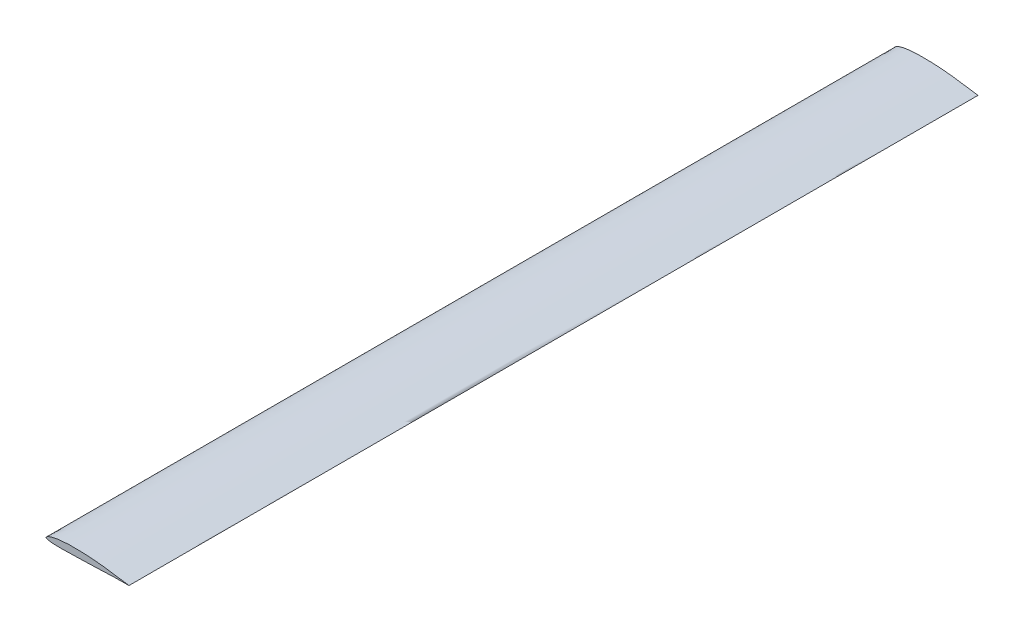
SolidWorks part; units mm, degrees
material "EPP"
ref_plane "Front Plane" through (0, 0, 0) normal (0, 0, 1) x (1, 0, 0)
ref_plane "Top Plane" through (0, 0, 0) normal (0, 1, 0) x (1, 0, 0)
ref_plane "Right Plane" through (0, 0, 0) normal (1, 0, 0) x (0, 0, -1)
curve "Curve1"
  spline degree 3 poles (174.7733, 0.0316, 0) (176.3111, -0.0187, 0) (174.7757, 0.116, 0) (173.5399, 0.2928, 0) (170.5766, 0.6845, 0) (166.994, 1.2316, 0) (162.3909, 1.9531, 0) (157.0465, 2.8136, 0) (150.9809, 3.7843, 0) (144.3051, 4.8259, 0) (137.096, 5.8948, 0) (129.4315, 6.9383, 0) (121.3831, 7.9192, 0) (113.0236, 8.817, 0) (104.4335, 9.6175, 0) (95.705, 10.3199, 0) (86.9339, 10.9107, 0) (78.2102, 11.3525, 0) (69.6201, 11.6329, 0) (61.2465, 11.7525, 0) (53.1672, 11.6898, 0) (45.4565, 11.4373, 0) (38.1834, 11.0163, 0) (31.4143, 10.4177, 0) (25.2077, 9.6463, 0) (19.6117, 8.718, 0) (14.6681, 7.6521, 0) (10.4108, 6.4684, 0) (6.8656, 5.2, 0) (4.0438, 3.8827, 0) (1.9667, 2.5734, 0) (0.8028, 1.5368, 0) (0.3168, 0.8428, 0) (0.1437, 0.5358, 0) (0.0368, 0.2599, 0) (-0.0054, 0.0423, 0) (0.0031, -0.1291, 0) (0.087, -0.2829, 0) (0.2444, -0.4592, 0) (0.4965, -0.6637, 0) (1.1068, -1.0427, 0) (2.4658, -1.5967, 0) (4.8509, -2.2112, 0) (8.2278, -2.7728, 0) (12.4572, -3.2321, 0) (17.5091, -3.5742, 0) (23.3419, -3.7993, 0) (29.9045, -3.9095, 0) (37.1348, -3.9142, 0) (44.9601, -3.8255, 0) (53.2979, -3.657, 0) (62.0571, -3.4223, 0) (71.1404, -3.1348, 0) (80.4454, -2.8077, 0) (89.8666, -2.4532, 0) (99.2959, -2.0855, 0) (108.6238, -1.7165, 0) (117.7405, -1.3609, 0) (126.5364, -1.0292, 0) (134.9041, -0.7323, 0) (142.7395, -0.4782, 0) (149.9393, -0.2762, 0) (156.4149, -0.1283, 0) (162.0529, -0.0322, 0) (166.8444, 0.0152, 0) (170.5231, 0.0337, 0) (173.5263, 0.0148, 0) (174.7733, 0.0316, 0) (176.3111, -0.0187, 0) (174.7757, 0.116, 0) knots -0.014204 -0.006419 -0.001632 0 0.001631 0.006435 0.014221 0.024766 0.037827 0.053149 0.070474 0.089536 0.110075 0.13186 0.154693 0.178371 0.20268 0.227364 0.252133 0.276728 0.300939 0.324527 0.347267 0.368992 0.389507 0.408628 0.426224 0.442179 0.456396 0.468805 0.479372 0.488086 0.494968 0.500034 0.501036 0.502094 0.502997 0.503513 0.503956 0.504409 0.504955 0.505943 0.50713 0.510998 0.518232 0.527846 0.539809 0.554056 0.57049 0.588974 0.609342 0.631393 0.654894 0.67959 0.705203 0.731447 0.75802 0.78462 0.810936 0.836657 0.861473 0.885081 0.907188 0.927507 0.945765 0.961712 0.975122 0.985796 0.993581 0.998368 1 1.001631 1.006435 1.014221 periodic
sketch "Sketch1" plane through (0, 0, 0) normal (0, 0, 1) x (1, 0, 0)
  spline S0 degree 3 poles (174.7733, 0.0316) (176.3111, -0.0187) (174.7757, 0.116) (173.5399, 0.2928) (170.5766, 0.6845) (166.994, 1.2316) (162.3909, 1.9531) (157.0465, 2.8136) (150.9809, 3.7843) (144.3051, 4.8259) (137.096, 5.8948) (129.4315, 6.9383) (121.3831, 7.9192) (113.0236, 8.817) (104.4335, 9.6175) (95.705, 10.3199) (86.9339, 10.9107) (78.2102, 11.3525) (69.6201, 11.6329) (61.2465, 11.7525) (53.1672, 11.6898) (45.4565, 11.4373) (38.1834, 11.0163) (31.4143, 10.4177) (25.2077, 9.6463) (19.6117, 8.718) (14.6681, 7.6521) (10.4108, 6.4684) (6.8656, 5.2) (4.0438, 3.8827) (1.9667, 2.5734) (0.8028, 1.5368) (0.3168, 0.8428) (0.1437, 0.5358) (0.0368, 0.2599) (-0.0054, 0.0423) (0.0031, -0.1291) (0.087, -0.2829) (0.2444, -0.4592) (0.4965, -0.6637) (1.1068, -1.0427) (2.4658, -1.5967) (4.8509, -2.2112) (8.2278, -2.7728) (12.4572, -3.2321) (17.5091, -3.5742) (23.3419, -3.7993) (29.9045, -3.9095) (37.1348, -3.9142) (44.9601, -3.8255) (53.2979, -3.657) (62.0571, -3.4223) (71.1404, -3.1348) (80.4454, -2.8077) (89.8666, -2.4532) (99.2959, -2.0855) (108.6238, -1.7165) (117.7405, -1.3609) (126.5364, -1.0292) (134.9041, -0.7323) (142.7395, -0.4782) (149.9393, -0.2762) (156.4149, -0.1283) (162.0529, -0.0322) (166.8444, 0.0152) (170.5231, 0.0337) (173.5263, 0.0148) (174.7733, 0.0316) (176.3111, -0.0187) (174.7757, 0.116) knots -0.014204 -0.006419 -0.001632 0 0.001631 0.006435 0.014221 0.024766 0.037827 0.053149 0.070474 0.089536 0.110075 0.13186 0.154693 0.178371 0.20268 0.227364 0.252133 0.276728 0.300939 0.324527 0.347267 0.368992 0.389507 0.408628 0.426224 0.442179 0.456396 0.468805 0.479372 0.488086 0.494968 0.500034 0.501036 0.502094 0.502997 0.503513 0.503956 0.504409 0.504955 0.505943 0.50713 0.510998 0.518232 0.527846 0.539809 0.554056 0.57049 0.588974 0.609342 0.631393 0.654894 0.67959 0.705203 0.731447 0.75802 0.78462 0.810936 0.836657 0.861473 0.885081 0.907188 0.927507 0.945765 0.961712 0.975122 0.985796 0.993581 0.998368 1 1.001631 1.006435 1.014221 only from (176, 0) to (176, 0) construction
  spline S1 degree 3 poles (174.7733, 0.0316) (176.3111, -0.0187) (174.7757, 0.116) (173.5399, 0.2928) (170.5766, 0.6845) (166.994, 1.2316) (162.3909, 1.9531) (157.0465, 2.8136) (150.9809, 3.7843) (144.3051, 4.8259) (137.096, 5.8948) (129.4315, 6.9383) (121.3831, 7.9192) (113.0236, 8.817) (104.4335, 9.6175) (95.705, 10.3199) (86.9339, 10.9107) (78.2102, 11.3525) (69.6201, 11.6329) (61.2465, 11.7525) (53.1672, 11.6898) (45.4565, 11.4373) (38.1834, 11.0163) (31.4143, 10.4177) (25.2077, 9.6463) (19.6117, 8.718) (14.6681, 7.6521) (10.4108, 6.4684) (6.8656, 5.2) (4.0438, 3.8827) (1.9667, 2.5734) (0.8028, 1.5368) (0.3168, 0.8428) (0.1437, 0.5358) (0.0368, 0.2599) (-0.0054, 0.0423) (0.0031, -0.1291) (0.087, -0.2829) (0.2444, -0.4592) (0.4965, -0.6637) (1.1068, -1.0427) (2.4658, -1.5967) (4.8509, -2.2112) (8.2278, -2.7728) (12.4572, -3.2321) (17.5091, -3.5742) (23.3419, -3.7993) (29.9045, -3.9095) (37.1348, -3.9142) (44.9601, -3.8255) (53.2979, -3.657) (62.0571, -3.4223) (71.1404, -3.1348) (80.4454, -2.8077) (89.8666, -2.4532) (99.2959, -2.0855) (108.6238, -1.7165) (117.7405, -1.3609) (126.5364, -1.0292) (134.9041, -0.7323) (142.7395, -0.4782) (149.9393, -0.2762) (156.4149, -0.1283) (162.0529, -0.0322) (166.8444, 0.0152) (170.5231, 0.0337) (173.5263, 0.0148) (174.7733, 0.0316) (176.3111, -0.0187) (174.7757, 0.116) knots -0.014204 -0.006419 -0.001632 0 0.001631 0.006435 0.014221 0.024766 0.037827 0.053149 0.070474 0.089536 0.110075 0.13186 0.154693 0.178371 0.20268 0.227364 0.252133 0.276728 0.300939 0.324527 0.347267 0.368992 0.389507 0.408628 0.426224 0.442179 0.456396 0.468805 0.479372 0.488086 0.494968 0.500034 0.501036 0.502094 0.502997 0.503513 0.503956 0.504409 0.504955 0.505943 0.50713 0.510998 0.518232 0.527846 0.539809 0.554056 0.57049 0.588974 0.609342 0.631393 0.654894 0.67959 0.705203 0.731447 0.75802 0.78462 0.810936 0.836657 0.861473 0.885081 0.907188 0.927507 0.945765 0.961712 0.975122 0.985796 0.993581 0.998368 1 1.001631 1.006435 1.014221 only from (176, 0) to (176, 0)
extrude "Boss-Extrude1" add sketch "Sketch1" along normal blind 1800
ref_plane "Plane1" through (0, 0, 0) normal (0, 1, 0) x (1, 0, 0)
sketch "Sketch2" plane through (0, 0, 0) normal (0, 1, 0) x (1, 0, 0)
  line L0 (87.9998, -1800) -> (87.9998, 0) construction
  line L1 (-0.0003, -1800) -> (176, -1800) construction
  line L2 (176, 0) -> (-0.0003, 0) construction
  line L3 (-0.0003, -900) -> (176, -900) construction
  line L4 (-0.0003, 0) -> (-0.0003, -1800) construction
  line L5 (176, -1800) -> (176, 0) construction
  line L7 (42.9998, -895) -> (132.9998, -895)
  line L8 (42.9998, -895) -> (42.9998, -905)
  line L9 (42.9998, -905) -> (132.9998, -905)
  line L10 (132.9998, -895) -> (132.9998, -905)
  line L11 (42.9998, -895) -> (132.9998, -905) construction
  line L12 (42.9998, -905) -> (132.9998, -895) construction
  point P12 (87.9998, -900)
  dimension "D1" = 10
  dimension "D2" = 90
extrude "Boss-Extrude2" add sketch "Sketch2" against normal blind 5
